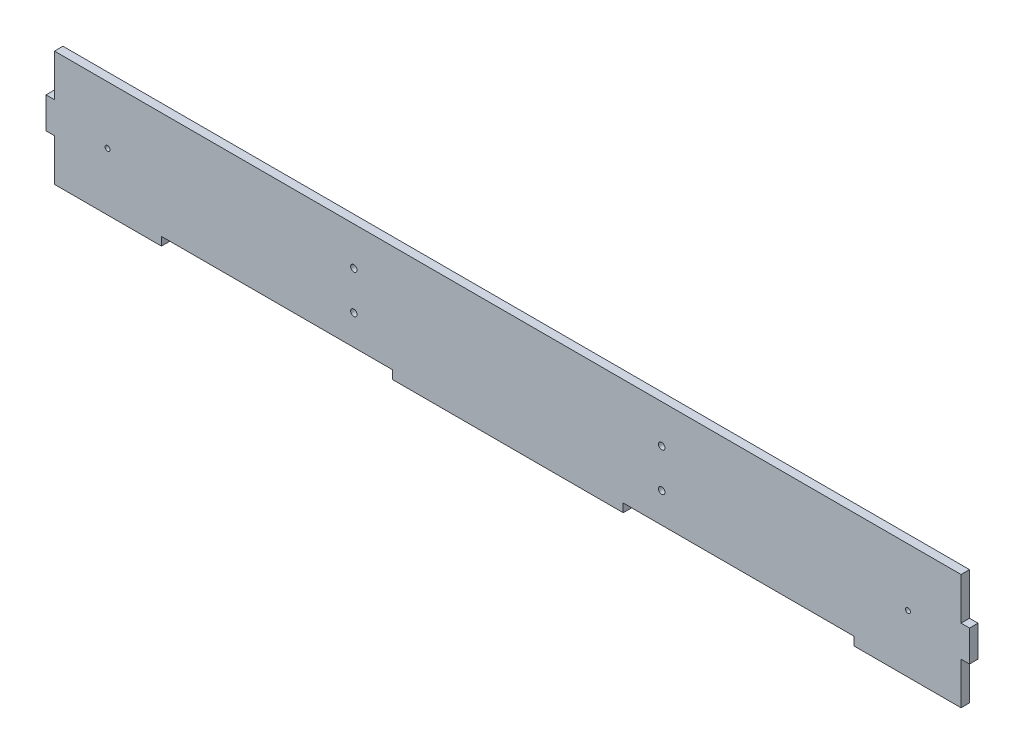
SolidWorks part; units mm, degrees
ref_plane "Front Plane" through (0, 0, 0) normal (0, 0, 1) x (1, 0, 0)
ref_plane "Top Plane" through (0, 0, 0) normal (0, 1, 0) x (1, 0, 0)
ref_plane "Right Plane" through (0, 0, 0) normal (1, 0, 0) x (0, 0, -1)
sketch "Sketch1" plane through (0, 0, 0) normal (0, 0, 1) x (1, 0, 0)
  line L0 (308.5, 78) -> (308.5, 50.625)
  line L1 (308.5, 50.625) -> (303, 50.625)
  line L2 (303, 50.625) -> (303, 42.125)
  line L3 (303, 42.125) -> (306.25, 42.125)
  line L4 (306.25, 42.125) -> (306.25, 40.5)
  line L5 (306.25, 40.5) -> (306.25, 38.875)
  line L6 (306.25, 38.875) -> (303, 38.875)
  line L7 (303, 38.875) -> (303, 30.375)
  line L8 (303, 30.375) -> (308.5, 30.375)
  line L9 (308.5, 30.375) -> (308.5, 3)
  line L10 (308.5, 3) -> (378, 3)
  line L11 (378, 3) -> (378, 8.5)
  line L12 (378, 8.5) -> (451.375, 8.5)
  line L13 (451.375, 8.5) -> (451.375, 17.95)
  line L14 (451.375, 17.95) -> (450.125, 17.95)
  line L15 (450.125, 17.95) -> (450.125, 20.6)
  line L16 (450.125, 20.6) -> (451.375, 20.6)
  line L17 (451.375, 20.6) -> (451.375, 23.25)
  line L18 (451.375, 23.25) -> (454.625, 23.25)
  line L19 (454.625, 23.25) -> (454.625, 20.6)
  line L20 (454.625, 20.6) -> (455.875, 20.6)
  line L21 (455.875, 20.6) -> (455.875, 17.95)
  line L22 (455.875, 17.95) -> (454.625, 17.95)
  line L23 (454.625, 17.95) -> (454.625, 8.5)
  line L24 (454.625, 8.5) -> (528, 8.5)
  line L25 (528, 8.5) -> (528, 3)
  line L26 (528, 3) -> (678, 3)
  line L27 (678, 3) -> (678, 8.5)
  line L28 (678, 8.5) -> (751.375, 8.5)
  line L29 (751.375, 8.5) -> (751.375, 17.95)
  line L30 (751.375, 17.95) -> (750.125, 17.95)
  line L31 (750.125, 17.95) -> (750.125, 20.6)
  line L32 (750.125, 20.6) -> (751.375, 20.6)
  line L33 (751.375, 20.6) -> (751.375, 23.25)
  line L34 (751.375, 23.25) -> (754.625, 23.25)
  line L35 (754.625, 23.25) -> (754.625, 20.6)
  line L36 (754.625, 20.6) -> (755.875, 20.6)
  line L37 (755.875, 20.6) -> (755.875, 17.95)
  line L38 (755.875, 17.95) -> (754.625, 17.95)
  line L39 (754.625, 17.95) -> (754.625, 8.5)
  line L40 (754.625, 8.5) -> (828, 8.5)
  line L41 (828, 8.5) -> (828, 3)
  line L42 (828, 3) -> (897.5, 3)
  line L43 (897.5, 3) -> (897.5, 30.375)
  line L44 (897.5, 30.375) -> (903, 30.375)
  line L45 (903, 30.375) -> (903, 38.875)
  line L46 (903, 38.875) -> (899.75, 38.875)
  line L47 (899.75, 38.875) -> (899.75, 40.5)
  line L48 (899.75, 40.5) -> (899.75, 42.125)
  line L49 (899.75, 42.125) -> (903, 42.125)
  line L50 (903, 42.125) -> (903, 50.625)
  line L51 (903, 50.625) -> (897.5, 50.625)
  line L52 (897.5, 50.625) -> (897.5, 78)
  line L53 (897.5, 78) -> (308.5, 78)
extrude "Boss-Extrude1" add sketch "Sketch1" along normal blind 5.5
sketch "Sketch2" plane through (0, 0, 5.5) normal (0, 0, 1) x (1, 0, 0)
  line L0 (897.5, 78) -> (308.5, 78) construction
  line L1 (503, 53) -> (703, 53)
  line L2 (503, 53) -> (503, 28)
  line L3 (503, 28) -> (703, 28)
  line L4 (703, 53) -> (703, 28)
  circle A0 centre (503, 53) radius 2.1
  circle A1 centre (503, 28) radius 2.1
  circle A2 centre (703, 28) radius 2.1
  circle A3 centre (703, 53) radius 2.1
  point P4 (603, 53)
  point P7 (603, 78)
  dimension "D4" = 4.2
  dimension "D1" = 25
  dimension "D2" = 200
  dimension "D3" = 25
extrude "Cut-Extrude1" cut sketch "Sketch2" against normal through all contours A0 | A1 | A2 | A3
sketch "Sketch3" plane through (0, 0, 5.5) normal (0, 0, 1) x (1, 0, 0)
  line L0 (306.25, 42.125) -> (306.25, 38.875) construction
  line L1 (303, 50.625) -> (303, 42.125) construction
  line L2 (903, 42.125) -> (903, 50.625) construction
  circle A0 centre (343, 40.5) radius 1.6
  circle A1 centre (863, 40.5) radius 1.6
  point P7 (306.25, 40.5)
  dimension "D1" = 3.2
  dimension "D2" = 40
  dimension "D3" = 40
extrude "Cut-Extrude2" cut sketch "Sketch3" against normal through all
sketch "Sketch4" plane through (0, 0, 5.5) normal (0, 0, 1) x (1, 0, 0)
  line L1 (303, 42.125) -> (306.25, 42.125)
  line L2 (303, 42.125) -> (303, 38.875)
  line L3 (303, 38.875) -> (306.25, 38.875)
  line L4 (306.25, 42.125) -> (306.25, 38.875)
  line L5 (454.625, 8.5) -> (451.375, 8.5)
  line L6 (454.625, 8.5) -> (454.625, 23.25)
  line L7 (454.625, 23.25) -> (451.375, 23.25)
  line L8 (451.375, 8.5) -> (451.375, 23.25)
  line L9 (450.125, 20.6) -> (455.875, 20.6)
  line L10 (450.125, 20.6) -> (450.125, 17.95)
  line L11 (450.125, 17.95) -> (455.875, 17.95)
  line L12 (455.875, 20.6) -> (455.875, 17.95)
  line L13 (754.625, 8.5) -> (751.375, 8.5)
  line L14 (754.625, 8.5) -> (754.625, 23.25)
  line L15 (754.625, 23.25) -> (751.375, 23.25)
  line L16 (751.375, 8.5) -> (751.375, 23.25)
  line L17 (750.125, 20.6) -> (755.875, 20.6)
  line L18 (750.125, 20.6) -> (750.125, 17.95)
  line L19 (750.125, 17.95) -> (755.875, 17.95)
  line L20 (755.875, 20.6) -> (755.875, 17.95)
  line L21 (899.75, 42.125) -> (903, 42.125)
  line L22 (899.75, 42.125) -> (899.75, 38.875)
  line L23 (899.75, 38.875) -> (903, 38.875)
  line L24 (903, 42.125) -> (903, 38.875)
extrude "Boss-Extrude2" add sketch "Sketch4" against normal up to surface (5.5 mm away) contours L4 L1 L2 L3 | L11 L8 L5 L6 | L8 L11 L6 L9 | L10 L11 L8 L9 | L8 L9 L6 L7 | L12 L9 L6 L11 | L24 L21 L22 L23 | L19 L16 L13 L14 | L16 L19 L14 L17 | L18 L19 L16 L17 | L16 L17 L14 L15 | L20 L17 L14 L19 region at (304.625, 40.5, 5.5) region at (453, 13.225, 5.5) region at (453, 19.275, 5.5) region at (455.25, 19.275, 5.5) region at (450.75, 19.275, 5.5) region at (453, 21.925, 5.5) region at (753, 13.225, 5.5) region at (753, 19.275, 5.5) region at (755.25, 19.275, 5.5) region at (750.75, 19.275, 5.5) region at (753, 21.925, 5.5) region at (901.375, 40.5, 5.5) up to face at (344.6, 40.5, 0)
